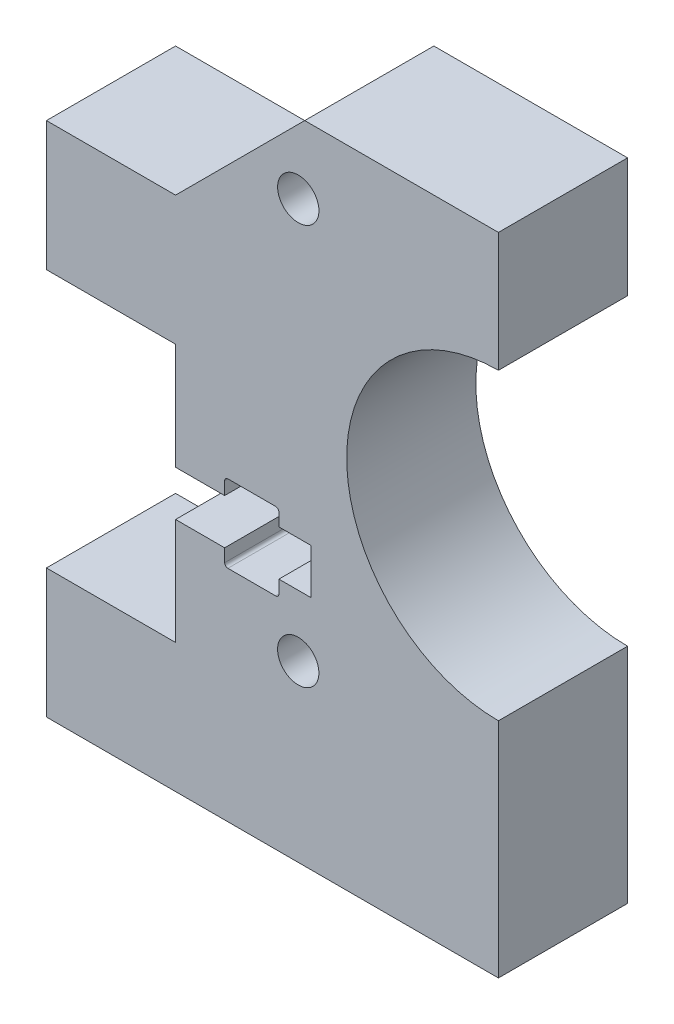
SolidWorks part; units mm, degrees
ref_plane "Front Plane" through (0, 0, 0) normal (0, 0, 1) x (1, 0, 0)
ref_plane "Top Plane" through (0, 0, 0) normal (0, 1, 0) x (1, 0, 0)
ref_plane "Right Plane" through (0, 0, 0) normal (1, 0, 0) x (0, 0, -1)
sketch "Sketch1" plane through (0, 0, 0) normal (0, 0, 1) x (1, 0, 0)
  line L0 (0, 0) -> (0, -60) construction
  line L1 (-10, -45) -> (0, -45) construction
  line L2 (25, -60) -> (25, 0) construction
  line L3 (25, 0) -> (0, 0) construction
  line L4 (0, 0) -> (0, -10)
  line L5 (0, -10) -> (-10, -10)
  line L6 (-10, -10) -> (-10, -20)
  line L7 (-10, -20) -> (0, -20)
  line L8 (0, -20) -> (0, -40)
  line L9 (25, -60) -> (0, -60) construction
  line L10 (0, -60) -> (25, -60)
  line L11 (-10, -40) -> (0, -40)
  line L12 (-10, -50) -> (-10, -40)
  line L13 (0, -50) -> (-10, -50)
  line L14 (25, -60) -> (25, 0)
  line L15 (0, 0) -> (25, 0)
  line L16 (0, -60) -> (0, -50)
  line L17 (-10, -15) -> (0, -15) construction
  line L18 (0, -30) -> (25, -30) construction
  dimension "D1" = 10
  dimension "D6" = 25
  dimension "D2" = 30
extrude "Boss-Extrude1" add sketch "Sketch1" along normal blind 10
sketch "Sketch2" plane through (0, 0, 10) normal (0, 0, 1) x (1, 0, 0)
  line L0 (25, -21) -> (0, -21) construction
  line L1 (25, -60) -> (25, 0) construction
  line L2 (0, -20) -> (0, -40) construction
  line L3 (25, -21) -> (9.5, -5.5) construction
  line L4 (25, -21) -> (9.5, -36.5) construction
  circle A0 centre (25, -21) radius 11.75
  circle A1 centre (9.5, -5.5) radius 1.6
  circle A2 centre (9.5, -36.5) radius 1.6
  point P6 (0, -30)
  dimension "D2" = 23.5
  dimension "D5" = 3.2
  dimension "D1" = 9
  dimension "D3" = 45
  dimension "D4" = 15.5
extrude "motor" cut sketch "Sketch2" against normal through all
sketch "Sketch3" plane through (0, 0, 10) normal (0, 0, 1) x (1, 0, 0)
  line L0 (0, -30) -> (10.5, -30) construction
  line L1 (0, -20) -> (0, -40) construction
  line L2 (10.5, -31.75) -> (10.5, -28.25) construction
  line L3 (10.5, -28.25) -> (0, -28.25) construction
  line L4 (0, -31.75) -> (0, -28.25)
  line L5 (0, -28.25) -> (3.8, -28.25)
  line L6 (3.8, -28.25) -> (3.8, -27.25)
  line L7 (4.05, -27) -> (7.75, -27)
  line L8 (8, -27.25) -> (8, -28.25)
  line L9 (8, -28.25) -> (10.5, -28.25)
  line L10 (10.5, -28.25) -> (10.5, -31.75)
  line L11 (10.5, -31.75) -> (0, -31.75) construction
  line L12 (8, -31.75) -> (10.5, -31.75)
  line L13 (8, -32.75) -> (8, -31.75)
  line L14 (4.05, -33) -> (7.75, -33)
  line L15 (3.8, -31.75) -> (3.8, -32.75)
  line L16 (0, -31.75) -> (3.8, -31.75)
  arc A0 (4.05, -33) -> (3.8, -32.75) centre (4.05, -32.75) cw
  arc A1 (8, -32.75) -> (7.75, -33) centre (7.75, -32.75) cw
  arc A2 (7.75, -27) -> (8, -27.25) centre (7.75, -27.25) cw
  arc A3 (3.8, -27.25) -> (4.05, -27) centre (4.05, -27.25) cw
  point P18 (3.8, -33)
  point P21 (8, -33)
  point P24 (8, -27)
  point P27 (3.8, -27)
  dimension "D6" = 0.25
  dimension "D1" = 1.75
  dimension "D2" = 8
  dimension "D3" = 10.5
  dimension "D4" = 3
  dimension "D5" = 4.2
extrude "screw" cut sketch "Sketch3" against normal through all
sketch "Sketch4" plane through (0, 0, 10) normal (0, 0, 1) x (1, 0, 0)
  line L0 (0, -50) -> (25, -50)
  line L1 (25, -60) -> (25, -32.75) construction
  line L2 (25, -50) -> (25, -60)
  line L3 (25, -60) -> (0, -60)
  line L4 (0, -60) -> (0, -50)
  line L5 (0, -10) -> (10, 0)
  line L6 (25, 0) -> (0, 0) construction
  line L7 (10, 0) -> (0, 0)
  line L8 (0, 0) -> (0, -10)
  dimension "D1" = 45
extrude "Cut-Extrude3" cut sketch "Sketch4" against normal through all
equation "\"X-ROD-SPACING\"=45"
equation "\"Y-ROD-SPACING\"=75"
equation "\"Z-ROD-SPACING\"=17.5"
equation "\"Y-BED-OFFSET\"=2"
equation "\"Y-BED-ROD-INSET\"=3.5"
equation "\"T-SLOT-NUT-FILLET-RADIUS\"=0.25"
equation "\"T-SLOT-SCREW-SHAFT-RADIUS\"=1.75"
equation "\"T-SLOT-SCREW-SHAFT-CUTOUT-LENGTH\"=10.5"
equation "\"T-SLOT-NUT-DEPTH\"=4.2"
equation "\"T-SLOT-NUT-WIDTH\"=3"
equation "\"T-SLOT-NUT-END-DISTANCE\"=8"
equation "\"ACRYLIC-THICKNESS\"=10"
equation "\"ACRYLIC-THICKNESS2\"=4.5"
equation "\"ACRYLIC-TAB-CUTOUT-SIZE\"=\"ACRYLIC-THICKNESS\"+\"ACRYLIC-TAB-TOLERANCE\"*2"
equation "\"ACRYLIC-TAB-WIDTH\"=\"ACRYLIC-THICKNESS\""
equation "\"ACRYLIC-M3-HOLE\"=3.2"
equation "\"SMOOTHROD-CAP-SCREW-DISTANCE\"=20"
equation "\"FRAME-WIDTH-INNER\"=370"
equation "\"NEMA17-HOLE-SPACING\"=31"
equation "\"NEMA17-CENTRAL-CUTOUT\"=22.5"
equation "\"Z-BRACKET-REACH\"=55"
equation "\"TOP-BRACKET-SPACING\"=40"
equation "\"SMOOTHROD-X-LENGTH\"=350"
equation "\"SMOOTHROD-Y-LENGTH\"=350"
equation "\"SMOOTHROD-Z-LENGTH\"=350"
equation "\"SMOOTHROD-TIGHTENING-HEADROOM\"=1"
equation "\"LEADSCREW-Z-LENGTH\"=300"
equation "\"SCREW-LENGTH-FRAME\"=\"ACRYLIC-THICKNESS\" + 10"
equation "\"SCREW-HEAD-RADIUS\"=6"
equation "\"PRINTED-X-SMOOTHROD-DIAMETER\"=8.2"
equation "\"PRINTED-X-SMOOTHROD-CUTOUT\"=10"
equation "\"PRINTED-X-BASE-HEIGHT\"=10"
equation "\"PRINTED-LM8UU-CUTOUT-SIZE\"=16"
equation "\"PRINTED-LM8UU-CUTOUT-LENGTH\"=24.5"
equation "\"PRINTED-X-IDLER-HEIGHT\"=16"
equation "\"PSU-MOUNTING-WIDTH\"=95"
equation "\"PSU-MOUNTING-HEIGHT\"=177"
equation "\"D1@Sketch1\"=10"
equation "\"D3@Sketch1\"=10"
equation "\"D1@Boss-Extrude1\"=\"ACRYLIC-THICKNESS\""
equation "\"D2@Sketch2\"=\"NEMA17-CENTRAL-CUTOUT\"+1"
equation "\"D4@Sketch2\"=\"NEMA17-HOLE-SPACING\"/2"
equation "\"D5@Sketch2\"=\"ACRYLIC-M3-HOLE\""
equation "\"D1@Sketch3\"=\"T-SLOT-SCREW-SHAFT-RADIUS\""
equation "\"D3@Sketch3\"=\"T-SLOT-SCREW-SHAFT-CUTOUT-LENGTH\""
equation "\"D4@Sketch3\"=\"T-SLOT-NUT-WIDTH\""
equation "\"D2@Sketch3\"=\"T-SLOT-NUT-END-DISTANCE\""
equation "\"D5@Sketch3\"=\"T-SLOT-NUT-DEPTH\""
equation "\"D6@Sketch3\"=\"T-SLOT-NUT-FILLET-RADIUS\""
